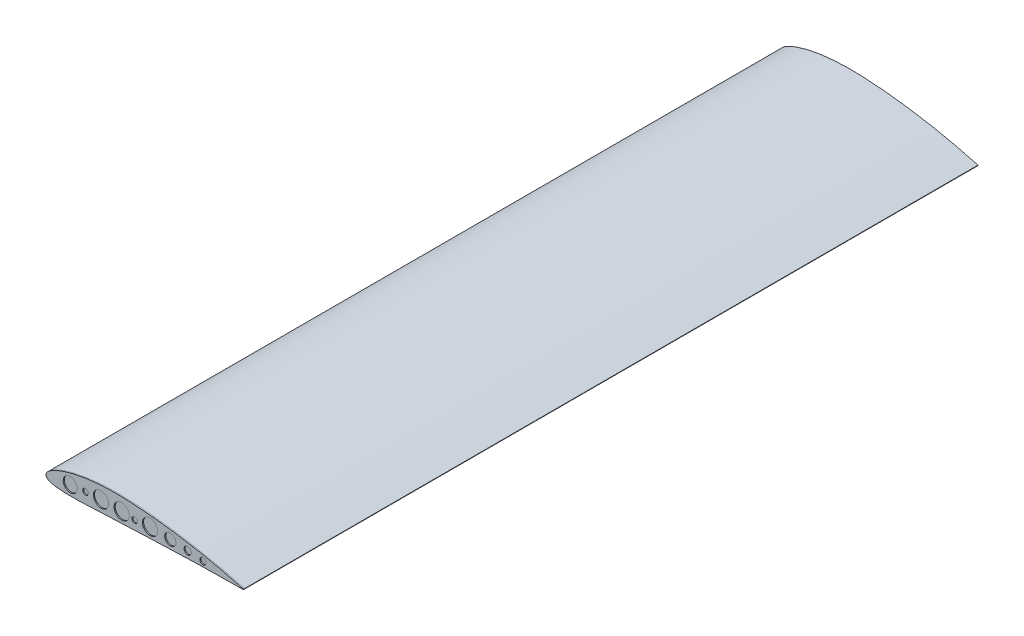
SolidWorks part; units mm, degrees
ref_plane "Спереди" through (0, 0, 0) normal (0, 0, 1) x (1, 0, 0)
ref_plane "Сверху" through (0, 0, 0) normal (0, 1, 0) x (1, 0, 0)
ref_plane "Справа" through (0, 0, 0) normal (1, 0, 0) x (0, 0, -1)
curve "Кривая1"
curve "Кривая2"
sketch "Эскиз1" plane through (0, 0, 0) normal (0, 0, 1) x (1, 0, 0)
  line L0 (350.0584, 0.4371) -> (349.9416, -0.4371)
  circle A0 centre (70, 10) radius 5
  circle A1 centre (157, 10) radius 5
  circle A2 centre (97.4967, 11.9444) radius 13.5
  circle A3 centre (134.0963, 11.9444) radius 13.5
  circle A4 centre (184.4175, 13.3257) radius 13.5
  circle A5 centre (42.9468, 7.3349) radius 12.5
  circle A6 centre (220.2781, 11.9444) radius 10
  circle A7 centre (251.1343, 10) radius 6.5
  circle A8 centre (278.0232, 7.3349) radius 5.5
  spline S0 degree 3 poles (-5446.8715, -2508.7969) (126.1492, 106.222) (-12.8915, 15.5996) (1.5868, -3.0408) (3.1128, -4.3174) (5.0932, -5.4477) (7.5057, -6.4459) (10.3511, -7.3163) (13.6202, -8.0629) (17.3047, -8.6899) (21.3937, -9.1993) (25.8754, -9.5951) (30.7367, -9.8833) (35.9641, -10.0678) (41.543, -10.1552) (47.4587, -10.1522) (53.6956, -10.0664) (60.2378, -9.9063) (67.069, -9.6797) (74.1728, -9.3973) (81.5318, -9.0687) (89.129, -8.7036) (96.9465, -8.3134) (104.9664, -7.9081) (113.1699, -7.4992) (121.5381, -7.0971) (130.0513, -6.7116) (138.7305, -6.3544) (147.5613, -6.023) (156.5187, -5.6608) (165.539, -5.2899) (174.5911, -4.913) (183.651, -4.5368) (192.6947, -4.1664) (201.6979, -3.8052) (210.6366, -3.4579) (219.4865, -3.1276) (228.2234, -2.8159) (236.8233, -2.526) (245.2625, -2.2578) (253.5175, -2.0131) (261.5654, -1.7909) (269.3836, -1.5915) (276.9501, -1.4144) (284.2431, -1.2577) (291.242, -1.1205) (297.9267, -1.0023) (304.2778, -0.8997) (310.2769, -0.8122) (315.9066, -0.7387) (321.1502, -0.6765) (325.9922, -0.6242) (330.4183, -0.5815) (334.4152, -0.5456) (337.971, -0.5171) (341.0748, -0.4941) (343.7174, -0.4754) (345.8906, -0.4615) (347.5879, -0.4511) (348.8039, -0.4436) (470.2745, 0.2435) (591.3157, 4.9751) (747.2137, -5974.9022) knots -0.181509 -0.181509 -0.181509 -0.181509 0.004621 0.009539 0.015079 0.02146 0.028815 0.037217 0.0467 0.057277 0.068945 0.081686 0.095481 0.110299 0.126106 0.142866 0.160538 0.179079 0.198444 0.218586 0.239458 0.261006 0.283182 0.305933 0.329205 0.352941 0.377085 0.40158 0.426714 0.452136 0.477716 0.503387 0.529081 0.554727 0.580259 0.605606 0.6307 0.655472 0.679854 0.703779 0.727181 0.749994 0.772155 0.793602 0.814272 0.834109 0.853054 0.871053 0.888055 0.904009 0.918869 0.932591 0.945134 0.956462 0.966538 0.975334 0.982823 0.988982 0.993791 0.997238 0.999309 2.025443 2.025443 2.025443 2.025443 only from (0, 0) to (349.9416, -0.4371) construction
  spline S1 degree 3 poles (2085.5087, 5741.6475) (435.8124, -34.4247) (394.0214, -11.7069) (348.9609, 0.741) (347.7876, 1.0648) (346.1489, 1.5135) (344.0486, 2.0844) (341.4919, 2.7716) (338.4852, 3.5709) (335.0354, 4.4738) (331.1514, 5.4747) (326.8426, 6.5647) (322.1195, 7.7348) (316.9943, 8.9771) (311.4795, 10.2804) (305.5895, 11.6361) (299.3393, 13.0339) (292.7446, 14.4627) (285.8231, 15.9138) (278.5923, 17.3751) (271.0714, 18.8365) (263.2804, 20.2892) (255.2397, 21.7208) (246.9711, 23.1239) (238.4966, 24.486) (229.8394, 25.8) (221.0228, 27.0546) (212.0713, 28.2428) (203.0092, 29.3543) (193.8618, 30.382) (184.6546, 31.3171) (175.4134, 32.1532) (166.1643, 32.8835) (156.9334, 33.5015) (147.7398, 34.0004) (138.5691, 34.3897) (129.4452, 34.5998) (120.4035, 34.6161) (111.5126, 34.4411) (102.8006, 34.0783) (94.2947, 33.5314) (86.0216, 32.8075) (78.0073, 31.9145) (70.2769, 30.8617) (62.8543, 29.6606) (55.7623, 28.3229) (49.0223, 26.8624) (42.6545, 25.2934) (36.677, 23.6312) (31.1071, 21.8907) (25.96, 20.0877) (21.2489, 18.2393) (16.9863, 16.3593) (13.1817, 14.4641) (9.8432, 12.5672) (6.9774, 10.6817) (4.5875, 8.8184) (2.6778, 6.9857) (1.2427, 5.1862) (0.3031, 3.4206) (-5.9667, -19.2767) (157.8244, -49.6104) (-5993.6515, 228.4557) knots -0.379848 -0.379848 -0.379848 -0.379848 0.000673 0.002688 0.00604 0.01072 0.016713 0.024005 0.032574 0.042394 0.053441 0.065681 0.079083 0.093606 0.109213 0.125858 0.143497 0.16208 0.181557 0.201873 0.222974 0.2448 0.267292 0.290389 0.314028 0.338143 0.362669 0.387537 0.412681 0.438032 0.463519 0.489073 0.514624 0.540102 0.565438 0.590624 0.615868 0.640767 0.665254 0.689266 0.712738 0.735606 0.757812 0.779295 0.8 0.819873 0.838862 0.85692 0.874001 0.890068 0.905081 0.91901 0.931831 0.943525 0.954082 0.963508 0.971818 0.979061 0.985315 0.990723 0.995508 1.175837 1.175837 1.175837 1.175837 only from (350.0584, 0.4371) to (0, 0) construction
  spline S2 degree 3 poles (0, 0) (0.1554, -0.5257) (0.4762, -1.611) (1.5868, -3.0408) (3.1128, -4.3174) (5.0932, -5.4477) (7.5057, -6.4459) (10.3511, -7.3163) (13.6202, -8.0629) (17.3047, -8.6899) (21.3937, -9.1993) (25.8754, -9.5951) (30.7367, -9.8833) (35.9641, -10.0678) (41.543, -10.1552) (47.4587, -10.1522) (53.6956, -10.0664) (60.2378, -9.9063) (67.069, -9.6797) (74.1728, -9.3973) (81.5318, -9.0687) (89.129, -8.7036) (96.9465, -8.3134) (104.9664, -7.9081) (113.1699, -7.4992) (121.5381, -7.0971) (130.0513, -6.7116) (138.7305, -6.3544) (147.5613, -6.023) (156.5187, -5.6608) (165.539, -5.2899) (174.5911, -4.913) (183.651, -4.5368) (192.6947, -4.1664) (201.6979, -3.8052) (210.6366, -3.4579) (219.4865, -3.1276) (228.2234, -2.8159) (236.8233, -2.526) (245.2625, -2.2578) (253.5175, -2.0131) (261.5654, -1.7909) (269.3836, -1.5915) (276.9501, -1.4144) (284.2431, -1.2577) (291.242, -1.1205) (297.9267, -1.0023) (304.2778, -0.8997) (310.2769, -0.8122) (315.9066, -0.7387) (321.1502, -0.6765) (325.9922, -0.6242) (330.4183, -0.5815) (334.4152, -0.5456) (337.971, -0.5171) (341.0748, -0.4941) (343.7174, -0.4754) (345.8906, -0.4615) (347.5879, -0.4511) (348.8039, -0.4436) (349.535, -0.4395) (349.8602, -0.4376) (349.9416, -0.4371) knots 0 0 0 0 0.004621 0.009539 0.015079 0.02146 0.028815 0.037217 0.0467 0.057277 0.068945 0.081686 0.095481 0.110299 0.126106 0.142866 0.160538 0.179079 0.198444 0.218586 0.239458 0.261006 0.283182 0.305933 0.329205 0.352941 0.377085 0.40158 0.426714 0.452136 0.477716 0.503387 0.529081 0.554727 0.580259 0.605606 0.6307 0.655472 0.679854 0.703779 0.727181 0.749994 0.772155 0.793602 0.814272 0.834109 0.853054 0.871053 0.888055 0.904009 0.918869 0.932591 0.945134 0.956462 0.966538 0.975334 0.982823 0.988982 0.993791 0.997238 0.999309 1 1 1 1
  spline S3 degree 3 poles (350.0584, 0.4371) (349.9799, 0.459) (349.6662, 0.5462) (348.9609, 0.741) (347.7876, 1.0648) (346.1489, 1.5135) (344.0486, 2.0844) (341.4919, 2.7716) (338.4852, 3.5709) (335.0354, 4.4738) (331.1514, 5.4747) (326.8426, 6.5647) (322.1195, 7.7348) (316.9943, 8.9771) (311.4795, 10.2804) (305.5895, 11.6361) (299.3393, 13.0339) (292.7446, 14.4627) (285.8231, 15.9138) (278.5923, 17.3751) (271.0714, 18.8365) (263.2804, 20.2892) (255.2397, 21.7208) (246.9711, 23.1239) (238.4966, 24.486) (229.8394, 25.8) (221.0228, 27.0546) (212.0713, 28.2428) (203.0092, 29.3543) (193.8618, 30.382) (184.6546, 31.3171) (175.4134, 32.1532) (166.1643, 32.8835) (156.9334, 33.5015) (147.7398, 34.0004) (138.5691, 34.3897) (129.4452, 34.5998) (120.4035, 34.6161) (111.5126, 34.4411) (102.8006, 34.0783) (94.2947, 33.5314) (86.0216, 32.8075) (78.0073, 31.9145) (70.2769, 30.8617) (62.8543, 29.6606) (55.7623, 28.3229) (49.0223, 26.8624) (42.6545, 25.2934) (36.677, 23.6312) (31.1071, 21.8907) (25.96, 20.0877) (21.2489, 18.2393) (16.9863, 16.3593) (13.1817, 14.4641) (9.8432, 12.5672) (6.9774, 10.6817) (4.5875, 8.8184) (2.6778, 6.9857) (1.2427, 5.1862) (0.3031, 3.4206) (-0.1802, 1.6712) (-0.0588, 0.5452) (0, 0) knots 0 0 0 0 0.000673 0.002688 0.00604 0.01072 0.016713 0.024005 0.032574 0.042394 0.053441 0.065681 0.079083 0.093606 0.109213 0.125858 0.143497 0.16208 0.181557 0.201873 0.222974 0.2448 0.267292 0.290389 0.314028 0.338143 0.362669 0.387537 0.412681 0.438032 0.463519 0.489073 0.514624 0.540102 0.565438 0.590624 0.615868 0.640767 0.665254 0.689266 0.712738 0.735606 0.757812 0.779295 0.8 0.819873 0.838862 0.85692 0.874001 0.890068 0.905081 0.91901 0.931831 0.943525 0.954082 0.963508 0.971818 0.979061 0.985315 0.990723 0.995508 1 1 1 1
  dimension "D1" = 10
  dimension "D2" = 10
  dimension "D7" = 25
  dimension "D8" = 27
  dimension "D9" = 27
  dimension "D10" = 27
  dimension "D11" = 20
  dimension "D12" = 13
  dimension "D13" = 11
  dimension "D3" = 10
  dimension "D4" = 70
  dimension "D5" = 157
  dimension "D6" = 10
  dimension "D14" = 7.3349
  dimension "D15" = 11.9444
  dimension "D16" = 27.0532
  dimension "D17" = 27.4967
  dimension "D18" = 36.5995
  dimension "D19" = 11.9444
  dimension "D20" = 27.4175
  dimension "D21" = 3.3257
  dimension "D22" = 35.8606
  dimension "D23" = 30.8562
  dimension "D24" = 10
  dimension "D25" = 2.6651
  dimension "D26" = 26.8889
  dimension "D27" = 1.9444
ref_plane "Плоскость8" through (0, 0, 162.5) normal (0, 0, 1) x (1, 0, 0)
ref_plane "Плоскость9" through (0, 0, 325) normal (0, 0, 1) x (1, 0, 0)
ref_plane "Плоскость10" through (0, 0, 487.5) normal (0, 0, 1) x (1, 0, 0)
ref_plane "Плоскость11" through (0, 0, 650) normal (0, 0, 1) x (1, 0, 0)
ref_plane "Плоскость12" through (0, 0, 812.5) normal (0, 0, 1) x (1, 0, 0)
ref_plane "Плоскость13" through (0, 0, 975) normal (0, 0, 1) x (1, 0, 0)
ref_plane "Плоскость14" through (0, 0, 1137.5) normal (0, 0, 1) x (1, 0, 0)
sketch "Эскиз4" plane through (0, 0, 162.5) normal (0, 0, 1) x (1, 0, 0)
  line L0 (350.0584, 0.4371) -> (349.9416, -0.4371)
  circle A0 centre (70, 10) radius 5
  circle A1 centre (157, 10) radius 5
  circle A2 centre (97.4967, 11.9444) radius 13.5
  circle A3 centre (134.0963, 11.9444) radius 13.5
  circle A4 centre (184.4175, 13.3257) radius 13.5
  circle A5 centre (42.9468, 7.3349) radius 12.5
  circle A6 centre (220.2781, 11.9444) radius 10
  circle A7 centre (251.1343, 10) radius 6.5
  circle A8 centre (278.0232, 7.3349) radius 5.5
  spline S2 degree 3 poles (0, 0) (0.1554, -0.5257) (0.4762, -1.611) (1.5868, -3.0408) (3.1128, -4.3174) (5.0932, -5.4477) (7.5057, -6.4459) (10.3511, -7.3163) (13.6202, -8.0629) (17.3047, -8.6899) (21.3937, -9.1993) (25.8754, -9.5951) (30.7367, -9.8833) (35.9641, -10.0678) (41.543, -10.1552) (47.4587, -10.1522) (53.6956, -10.0664) (60.2378, -9.9063) (67.069, -9.6797) (74.1728, -9.3973) (81.5318, -9.0687) (89.129, -8.7036) (96.9465, -8.3134) (104.9664, -7.9081) (113.1699, -7.4992) (121.5381, -7.0971) (130.0513, -6.7116) (138.7305, -6.3544) (147.5613, -6.023) (156.5187, -5.6608) (165.539, -5.2899) (174.5911, -4.913) (183.651, -4.5368) (192.6947, -4.1664) (201.6979, -3.8052) (210.6366, -3.4579) (219.4865, -3.1276) (228.2234, -2.8159) (236.8233, -2.526) (245.2625, -2.2578) (253.5175, -2.0131) (261.5654, -1.7909) (269.3836, -1.5915) (276.9501, -1.4144) (284.2431, -1.2577) (291.242, -1.1205) (297.9267, -1.0023) (304.2778, -0.8997) (310.2769, -0.8122) (315.9066, -0.7387) (321.1502, -0.6765) (325.9922, -0.6242) (330.4183, -0.5815) (334.4152, -0.5456) (337.971, -0.5171) (341.0748, -0.4941) (343.7174, -0.4754) (345.8906, -0.4615) (347.5879, -0.4511) (348.8039, -0.4436) (349.535, -0.4395) (349.8602, -0.4376) (349.9416, -0.4371) knots 0 0 0 0 0.004621 0.009539 0.015079 0.02146 0.028815 0.037217 0.0467 0.057277 0.068945 0.081686 0.095481 0.110299 0.126106 0.142866 0.160538 0.179079 0.198444 0.218586 0.239458 0.261006 0.283182 0.305933 0.329205 0.352941 0.377085 0.40158 0.426714 0.452136 0.477716 0.503387 0.529081 0.554727 0.580259 0.605606 0.6307 0.655472 0.679854 0.703779 0.727181 0.749994 0.772155 0.793602 0.814272 0.834109 0.853054 0.871053 0.888055 0.904009 0.918869 0.932591 0.945134 0.956462 0.966538 0.975334 0.982823 0.988982 0.993791 0.997238 0.999309 1 1 1 1
  spline S3 degree 3 poles (350.0584, 0.4372) (349.9799, 0.459) (349.6662, 0.5462) (348.9609, 0.741) (347.7876, 1.0648) (346.1489, 1.5135) (344.0486, 2.0844) (341.4919, 2.7716) (338.4852, 3.5709) (335.0354, 4.4738) (331.1514, 5.4747) (326.8426, 6.5647) (322.1195, 7.7348) (316.9943, 8.9771) (311.4795, 10.2804) (305.5895, 11.6361) (299.3393, 13.0339) (292.7446, 14.4627) (285.8231, 15.9138) (278.5923, 17.3751) (271.0714, 18.8365) (263.2804, 20.2892) (255.2397, 21.7208) (246.9711, 23.1239) (238.4966, 24.486) (229.8394, 25.8) (221.0228, 27.0546) (212.0713, 28.2428) (203.0092, 29.3543) (193.8618, 30.382) (184.6546, 31.3171) (175.4134, 32.1532) (166.1643, 32.8835) (156.9334, 33.5015) (147.7398, 34.0004) (138.5691, 34.3897) (129.4452, 34.5998) (120.4035, 34.6161) (111.5126, 34.4411) (102.8006, 34.0783) (94.2947, 33.5314) (86.0216, 32.8075) (78.0073, 31.9145) (70.2769, 30.8617) (62.8543, 29.6606) (55.7623, 28.3229) (49.0223, 26.8624) (42.6545, 25.2934) (36.677, 23.6312) (31.1071, 21.8907) (25.96, 20.0877) (21.2489, 18.2393) (16.9863, 16.3593) (13.1817, 14.4641) (9.8432, 12.5672) (6.9774, 10.6817) (4.5875, 8.8184) (2.6778, 6.9857) (1.2427, 5.1862) (0.3031, 3.4206) (-0.1802, 1.6712) (-0.0588, 0.5452) (0, 0) knots 0 0 0 0 0.000673 0.002688 0.00604 0.01072 0.016713 0.024005 0.032574 0.042394 0.053441 0.065681 0.079083 0.093606 0.109213 0.125858 0.143497 0.16208 0.181557 0.201873 0.222974 0.2448 0.267292 0.290389 0.314028 0.338143 0.362669 0.387537 0.412681 0.438032 0.463519 0.489073 0.514624 0.540102 0.565438 0.590624 0.615868 0.640767 0.665254 0.689266 0.712738 0.735606 0.757812 0.779295 0.8 0.819873 0.838862 0.85692 0.874001 0.890068 0.905081 0.91901 0.931831 0.943525 0.954082 0.963508 0.971818 0.979061 0.985315 0.990723 0.995508 1 1 1 1
  dimension "D1" = 10
  dimension "D2" = 10
  dimension "D7" = 25
  dimension "D8" = 27
  dimension "D9" = 27
  dimension "D10" = 27
  dimension "D11" = 20
  dimension "D12" = 13
  dimension "D13" = 11
  dimension "D3" = 10
  dimension "D4" = 70
  dimension "D5" = 157
  dimension "D6" = 10
  dimension "D14" = 7.3349
  dimension "D15" = 11.9444
  dimension "D16" = 27.0532
  dimension "D17" = 27.4967
  dimension "D18" = 36.5995
  dimension "D19" = 11.9444
  dimension "D20" = 27.4175
  dimension "D21" = 3.3257
  dimension "D22" = 35.8606
  dimension "D23" = 30.8562
  dimension "D24" = 10
  dimension "D25" = 2.6651
  dimension "D26" = 26.8889
  dimension "D27" = 1.9444
  dimension "D28" = 0.8743
  dimension "D29" = 349.9416
  dimension "D30" = 350.0584
  dimension "D32" = 0.4371
sketch "Эскиз5" plane through (0, 0, 325) normal (0, 0, 1) x (1, 0, 0)
  line L0 (350.0585, 0.4371) -> (349.9416, -0.4372)
  circle A0 centre (70, 10) radius 5
  circle A1 centre (157, 10) radius 5
  circle A2 centre (97.4967, 11.9444) radius 13.5
  circle A3 centre (134.0963, 11.9444) radius 13.5
  circle A4 centre (184.4175, 13.3257) radius 13.5
  circle A5 centre (42.9468, 7.3349) radius 12.5
  circle A6 centre (220.2781, 11.9444) radius 10
  circle A7 centre (251.1343, 10) radius 6.5
  circle A8 centre (278.0232, 7.3349) radius 5.5
  spline S2 degree 3 poles (0, 0) (0.1554, -0.5257) (0.4762, -1.611) (1.5868, -3.0408) (3.1128, -4.3174) (5.0932, -5.4477) (7.5057, -6.4459) (10.3511, -7.3163) (13.6202, -8.0629) (17.3047, -8.6899) (21.3937, -9.1993) (25.8754, -9.5951) (30.7367, -9.8833) (35.9641, -10.0678) (41.543, -10.1552) (47.4587, -10.1522) (53.6956, -10.0664) (60.2378, -9.9063) (67.069, -9.6797) (74.1728, -9.3973) (81.5318, -9.0687) (89.129, -8.7036) (96.9465, -8.3134) (104.9664, -7.9081) (113.1699, -7.4992) (121.5381, -7.0971) (130.0513, -6.7116) (138.7305, -6.3544) (147.5613, -6.023) (156.5187, -5.6608) (165.539, -5.2899) (174.5911, -4.913) (183.651, -4.5368) (192.6947, -4.1664) (201.6979, -3.8052) (210.6366, -3.4579) (219.4865, -3.1276) (228.2234, -2.8159) (236.8233, -2.526) (245.2625, -2.2578) (253.5175, -2.0131) (261.5654, -1.7909) (269.3836, -1.5915) (276.9501, -1.4144) (284.2431, -1.2577) (291.242, -1.1205) (297.9267, -1.0023) (304.2778, -0.8997) (310.2769, -0.8122) (315.9066, -0.7387) (321.1502, -0.6765) (325.9922, -0.6242) (330.4183, -0.5815) (334.4152, -0.5456) (337.971, -0.5171) (341.0748, -0.4941) (343.7174, -0.4754) (345.8906, -0.4615) (347.5879, -0.4511) (348.8039, -0.4436) (349.535, -0.4395) (349.8602, -0.4376) (349.9416, -0.4372) knots 0 0 0 0 0.004621 0.009539 0.015079 0.02146 0.028815 0.037217 0.0467 0.057277 0.068945 0.081686 0.095481 0.110299 0.126106 0.142866 0.160538 0.179079 0.198444 0.218586 0.239458 0.261006 0.283182 0.305933 0.329205 0.352941 0.377085 0.40158 0.426714 0.452136 0.477716 0.503387 0.529081 0.554727 0.580259 0.605606 0.6307 0.655472 0.679854 0.703779 0.727181 0.749994 0.772155 0.793602 0.814272 0.834109 0.853054 0.871053 0.888055 0.904009 0.918869 0.932591 0.945134 0.956462 0.966538 0.975334 0.982823 0.988982 0.993791 0.997238 0.999309 1 1 1 1
  spline S3 degree 3 poles (350.0585, 0.4371) (349.9799, 0.459) (349.6662, 0.5462) (348.9609, 0.741) (347.7876, 1.0648) (346.1489, 1.5135) (344.0486, 2.0844) (341.4919, 2.7716) (338.4852, 3.5709) (335.0354, 4.4738) (331.1514, 5.4747) (326.8426, 6.5647) (322.1195, 7.7348) (316.9943, 8.9771) (311.4795, 10.2804) (305.5895, 11.6361) (299.3393, 13.0339) (292.7446, 14.4627) (285.8231, 15.9138) (278.5923, 17.3751) (271.0714, 18.8365) (263.2804, 20.2892) (255.2397, 21.7208) (246.9711, 23.1239) (238.4966, 24.486) (229.8394, 25.8) (221.0228, 27.0546) (212.0713, 28.2428) (203.0092, 29.3543) (193.8618, 30.382) (184.6546, 31.3171) (175.4134, 32.1532) (166.1643, 32.8835) (156.9334, 33.5015) (147.7398, 34.0004) (138.5691, 34.3897) (129.4452, 34.5998) (120.4035, 34.6161) (111.5126, 34.4411) (102.8006, 34.0783) (94.2947, 33.5314) (86.0216, 32.8075) (78.0073, 31.9145) (70.2769, 30.8617) (62.8543, 29.6606) (55.7623, 28.3229) (49.0223, 26.8624) (42.6545, 25.2934) (36.677, 23.6312) (31.1071, 21.8907) (25.96, 20.0877) (21.2489, 18.2393) (16.9863, 16.3593) (13.1817, 14.4641) (9.8432, 12.5672) (6.9774, 10.6817) (4.5875, 8.8184) (2.6778, 6.9857) (1.2427, 5.1862) (0.3031, 3.4206) (-0.1802, 1.6712) (-0.0588, 0.5452) (0, 0) knots 0 0 0 0 0.000673 0.002688 0.00604 0.01072 0.016713 0.024005 0.032574 0.042394 0.053441 0.065681 0.079083 0.093606 0.109213 0.125858 0.143497 0.16208 0.181557 0.201873 0.222974 0.2448 0.267292 0.290389 0.314028 0.338143 0.362669 0.387537 0.412681 0.438032 0.463519 0.489073 0.514624 0.540102 0.565438 0.590624 0.615868 0.640767 0.665254 0.689266 0.712738 0.735606 0.757812 0.779295 0.8 0.819873 0.838862 0.85692 0.874001 0.890068 0.905081 0.91901 0.931831 0.943525 0.954082 0.963508 0.971818 0.979061 0.985315 0.990723 0.995508 1 1 1 1
  dimension "D1" = 10
  dimension "D2" = 10
  dimension "D7" = 25
  dimension "D8" = 27
  dimension "D9" = 27
  dimension "D10" = 27
  dimension "D11" = 20
  dimension "D12" = 13
  dimension "D13" = 11
  dimension "D3" = 10
  dimension "D4" = 70
  dimension "D5" = 157
  dimension "D6" = 10
  dimension "D14" = 7.3349
  dimension "D15" = 11.9444
  dimension "D16" = 27.0532
  dimension "D17" = 27.4967
  dimension "D18" = 36.5995
  dimension "D19" = 11.9444
  dimension "D20" = 27.4175
  dimension "D21" = 3.3257
  dimension "D22" = 35.8606
  dimension "D23" = 30.8562
  dimension "D24" = 10
  dimension "D25" = 2.6651
  dimension "D26" = 26.8889
  dimension "D27" = 1.9444
  dimension "D28" = 349.9416
  dimension "D29" = 350.0584
  dimension "D30" = 0.4371
  dimension "D31" = 0.8821
sketch "Эскиз6" plane through (0, 0, 487.5) normal (0, 0, 1) x (1, 0, 0)
  line L0 (350.0584, 0.4371) -> (349.9416, -0.4372)
  circle A0 centre (70, 10) radius 5
  circle A1 centre (157, 10) radius 5
  circle A2 centre (97.4967, 11.9444) radius 13.5
  circle A3 centre (134.0963, 11.9444) radius 13.5
  circle A4 centre (184.4175, 13.3257) radius 13.5
  circle A5 centre (42.9468, 7.3349) radius 12.5
  circle A6 centre (220.2781, 11.9444) radius 10
  circle A7 centre (251.1343, 10) radius 6.5
  circle A8 centre (278.0232, 7.3349) radius 5.5
  spline S2 degree 3 poles (0, 0) (0.1554, -0.5257) (0.4762, -1.611) (1.5868, -3.0408) (3.1128, -4.3174) (5.0932, -5.4477) (7.5057, -6.4459) (10.3511, -7.3163) (13.6202, -8.0629) (17.3047, -8.6899) (21.3937, -9.1993) (25.8754, -9.5951) (30.7367, -9.8833) (35.9641, -10.0678) (41.543, -10.1552) (47.4587, -10.1522) (53.6956, -10.0664) (60.2378, -9.9063) (67.069, -9.6797) (74.1728, -9.3973) (81.5318, -9.0687) (89.129, -8.7036) (96.9465, -8.3134) (104.9664, -7.9081) (113.1699, -7.4992) (121.5381, -7.0971) (130.0513, -6.7116) (138.7305, -6.3544) (147.5613, -6.023) (156.5187, -5.6608) (165.539, -5.2899) (174.5911, -4.913) (183.651, -4.5368) (192.6947, -4.1664) (201.6979, -3.8052) (210.6366, -3.4579) (219.4865, -3.1276) (228.2234, -2.8159) (236.8233, -2.526) (245.2625, -2.2578) (253.5175, -2.0131) (261.5654, -1.7909) (269.3836, -1.5915) (276.9501, -1.4144) (284.2431, -1.2577) (291.242, -1.1205) (297.9267, -1.0023) (304.2778, -0.8997) (310.2769, -0.8122) (315.9066, -0.7387) (321.1502, -0.6765) (325.9922, -0.6242) (330.4183, -0.5815) (334.4152, -0.5456) (337.971, -0.5171) (341.0748, -0.4941) (343.7174, -0.4754) (345.8906, -0.4615) (347.5879, -0.4511) (348.8039, -0.4436) (349.535, -0.4395) (349.8602, -0.4376) (349.9416, -0.4372) knots 0 0 0 0 0.004621 0.009539 0.015079 0.02146 0.028815 0.037217 0.0467 0.057277 0.068945 0.081686 0.095481 0.110299 0.126106 0.142866 0.160538 0.179079 0.198444 0.218586 0.239458 0.261006 0.283182 0.305933 0.329205 0.352941 0.377085 0.40158 0.426714 0.452136 0.477716 0.503387 0.529081 0.554727 0.580259 0.605606 0.6307 0.655472 0.679854 0.703779 0.727181 0.749994 0.772155 0.793602 0.814272 0.834109 0.853054 0.871053 0.888055 0.904009 0.918869 0.932591 0.945134 0.956462 0.966538 0.975334 0.982823 0.988982 0.993791 0.997238 0.999309 1 1 1 1
  spline S3 degree 3 poles (350.0584, 0.4371) (349.9799, 0.459) (349.6662, 0.5462) (348.9609, 0.741) (347.7876, 1.0648) (346.1489, 1.5135) (344.0486, 2.0844) (341.4919, 2.7716) (338.4852, 3.5709) (335.0354, 4.4738) (331.1514, 5.4747) (326.8426, 6.5647) (322.1195, 7.7348) (316.9943, 8.9771) (311.4795, 10.2804) (305.5895, 11.6361) (299.3393, 13.0339) (292.7446, 14.4627) (285.8231, 15.9138) (278.5923, 17.3751) (271.0714, 18.8365) (263.2804, 20.2892) (255.2397, 21.7208) (246.9711, 23.1239) (238.4966, 24.486) (229.8394, 25.8) (221.0228, 27.0546) (212.0713, 28.2428) (203.0092, 29.3543) (193.8618, 30.382) (184.6546, 31.3171) (175.4134, 32.1532) (166.1643, 32.8835) (156.9334, 33.5015) (147.7398, 34.0004) (138.5691, 34.3897) (129.4452, 34.5998) (120.4035, 34.6161) (111.5126, 34.4411) (102.8006, 34.0783) (94.2947, 33.5314) (86.0216, 32.8075) (78.0073, 31.9145) (70.2769, 30.8617) (62.8543, 29.6606) (55.7623, 28.3229) (49.0223, 26.8624) (42.6545, 25.2934) (36.677, 23.6312) (31.1071, 21.8907) (25.96, 20.0877) (21.2489, 18.2393) (16.9863, 16.3593) (13.1817, 14.4641) (9.8432, 12.5672) (6.9774, 10.6817) (4.5875, 8.8184) (2.6778, 6.9857) (1.2427, 5.1862) (0.3031, 3.4206) (-0.1802, 1.6712) (-0.0588, 0.5452) (0, 0) knots 0 0 0 0 0.000673 0.002688 0.00604 0.01072 0.016713 0.024005 0.032574 0.042394 0.053441 0.065681 0.079083 0.093606 0.109213 0.125858 0.143497 0.16208 0.181557 0.201873 0.222974 0.2448 0.267292 0.290389 0.314028 0.338143 0.362669 0.387537 0.412681 0.438032 0.463519 0.489073 0.514624 0.540102 0.565438 0.590624 0.615868 0.640767 0.665254 0.689266 0.712738 0.735606 0.757812 0.779295 0.8 0.819873 0.838862 0.85692 0.874001 0.890068 0.905081 0.91901 0.931831 0.943525 0.954082 0.963508 0.971818 0.979061 0.985315 0.990723 0.995508 1 1 1 1
  dimension "D1" = 10
  dimension "D2" = 10
  dimension "D7" = 25
  dimension "D8" = 27
  dimension "D9" = 27
  dimension "D10" = 27
  dimension "D11" = 20
  dimension "D12" = 13
  dimension "D13" = 11
  dimension "D3" = 10
  dimension "D4" = 70
  dimension "D5" = 157
  dimension "D6" = 10
  dimension "D14" = 7.3349
  dimension "D15" = 11.9444
  dimension "D16" = 27.0532
  dimension "D17" = 27.4967
  dimension "D18" = 36.5995
  dimension "D19" = 11.9444
  dimension "D20" = 27.4175
  dimension "D21" = 3.3257
  dimension "D22" = 35.8606
  dimension "D23" = 30.8562
  dimension "D24" = 10
  dimension "D25" = 2.6651
  dimension "D26" = 26.8889
  dimension "D27" = 1.9444
  dimension "D28" = 0.8821
  dimension "D29" = 349.9416
  dimension "D30" = 350.0587
  dimension "D31" = 0.4371
sketch "Эскиз7" plane through (0, 0, 650) normal (0, 0, 1) x (1, 0, 0)
  line L0 (350.0584, 0.4371) -> (349.9416, -0.4372)
  circle A0 centre (70, 10) radius 5
  circle A1 centre (157, 10) radius 5
  circle A2 centre (97.4967, 11.9444) radius 13.5
  circle A3 centre (134.0963, 11.9444) radius 13.5
  circle A4 centre (184.4175, 13.3257) radius 13.5
  circle A5 centre (42.9468, 7.3349) radius 12.5
  circle A6 centre (220.2781, 11.9444) radius 10
  circle A7 centre (251.1343, 10) radius 6.5
  circle A8 centre (278.0232, 7.3349) radius 5.5
  spline S2 degree 3 poles (0, 0) (0.1554, -0.5257) (0.4762, -1.611) (1.5868, -3.0408) (3.1128, -4.3174) (5.0932, -5.4477) (7.5057, -6.4459) (10.3511, -7.3163) (13.6202, -8.0629) (17.3047, -8.6899) (21.3937, -9.1993) (25.8754, -9.5951) (30.7367, -9.8833) (35.9641, -10.0678) (41.543, -10.1552) (47.4587, -10.1522) (53.6956, -10.0664) (60.2378, -9.9063) (67.069, -9.6797) (74.1728, -9.3973) (81.5318, -9.0687) (89.129, -8.7036) (96.9465, -8.3134) (104.9664, -7.9081) (113.1699, -7.4992) (121.5381, -7.0971) (130.0513, -6.7116) (138.7305, -6.3544) (147.5613, -6.023) (156.5187, -5.6608) (165.539, -5.2899) (174.5911, -4.913) (183.651, -4.5368) (192.6947, -4.1664) (201.6979, -3.8052) (210.6366, -3.4579) (219.4865, -3.1276) (228.2234, -2.8159) (236.8233, -2.526) (245.2625, -2.2578) (253.5175, -2.0131) (261.5654, -1.7909) (269.3836, -1.5915) (276.9501, -1.4144) (284.2431, -1.2577) (291.242, -1.1205) (297.9267, -1.0023) (304.2778, -0.8997) (310.2769, -0.8122) (315.9066, -0.7387) (321.1502, -0.6765) (325.9922, -0.6242) (330.4183, -0.5815) (334.4152, -0.5456) (337.971, -0.5171) (341.0748, -0.4941) (343.7174, -0.4754) (345.8906, -0.4615) (347.5879, -0.4511) (348.8039, -0.4436) (349.535, -0.4395) (349.8602, -0.4376) (349.9416, -0.4372) knots 0 0 0 0 0.004621 0.009539 0.015079 0.02146 0.028815 0.037217 0.0467 0.057277 0.068945 0.081686 0.095481 0.110299 0.126106 0.142866 0.160538 0.179079 0.198444 0.218586 0.239458 0.261006 0.283182 0.305933 0.329205 0.352941 0.377085 0.40158 0.426714 0.452136 0.477716 0.503387 0.529081 0.554727 0.580259 0.605606 0.6307 0.655472 0.679854 0.703779 0.727181 0.749994 0.772155 0.793602 0.814272 0.834109 0.853054 0.871053 0.888055 0.904009 0.918869 0.932591 0.945134 0.956462 0.966538 0.975334 0.982823 0.988982 0.993791 0.997238 0.999309 1 1 1 1
  spline S3 degree 3 poles (350.0584, 0.4371) (349.9799, 0.459) (349.6662, 0.5462) (348.9609, 0.741) (347.7876, 1.0648) (346.1489, 1.5135) (344.0486, 2.0844) (341.4919, 2.7716) (338.4852, 3.5709) (335.0354, 4.4738) (331.1514, 5.4747) (326.8426, 6.5647) (322.1195, 7.7348) (316.9943, 8.9771) (311.4795, 10.2804) (305.5895, 11.6361) (299.3393, 13.0339) (292.7446, 14.4627) (285.8231, 15.9138) (278.5923, 17.3751) (271.0714, 18.8365) (263.2804, 20.2892) (255.2397, 21.7208) (246.9711, 23.1239) (238.4966, 24.486) (229.8394, 25.8) (221.0228, 27.0546) (212.0713, 28.2428) (203.0092, 29.3543) (193.8618, 30.382) (184.6546, 31.3171) (175.4134, 32.1532) (166.1643, 32.8835) (156.9334, 33.5015) (147.7398, 34.0004) (138.5691, 34.3897) (129.4452, 34.5998) (120.4035, 34.6161) (111.5126, 34.4411) (102.8006, 34.0783) (94.2947, 33.5314) (86.0216, 32.8075) (78.0073, 31.9145) (70.2769, 30.8617) (62.8543, 29.6606) (55.7623, 28.3229) (49.0223, 26.8624) (42.6545, 25.2934) (36.677, 23.6312) (31.1071, 21.8907) (25.96, 20.0877) (21.2489, 18.2393) (16.9863, 16.3593) (13.1817, 14.4641) (9.8432, 12.5672) (6.9774, 10.6817) (4.5875, 8.8184) (2.6778, 6.9857) (1.2427, 5.1862) (0.3031, 3.4206) (-0.1802, 1.6712) (-0.0588, 0.5452) (0, 0) knots 0 0 0 0 0.000673 0.002688 0.00604 0.01072 0.016713 0.024005 0.032574 0.042394 0.053441 0.065681 0.079083 0.093606 0.109213 0.125858 0.143497 0.16208 0.181557 0.201873 0.222974 0.2448 0.267292 0.290389 0.314028 0.338143 0.362669 0.387537 0.412681 0.438032 0.463519 0.489073 0.514624 0.540102 0.565438 0.590624 0.615868 0.640767 0.665254 0.689266 0.712738 0.735606 0.757812 0.779295 0.8 0.819873 0.838862 0.85692 0.874001 0.890068 0.905081 0.91901 0.931831 0.943525 0.954082 0.963508 0.971818 0.979061 0.985315 0.990723 0.995508 1 1 1 1
  dimension "D1" = 10
  dimension "D2" = 10
  dimension "D7" = 25
  dimension "D8" = 27
  dimension "D9" = 27
  dimension "D10" = 27
  dimension "D11" = 20
  dimension "D12" = 13
  dimension "D13" = 11
  dimension "D3" = 10
  dimension "D4" = 70
  dimension "D5" = 157
  dimension "D6" = 10
  dimension "D14" = 7.3349
  dimension "D15" = 11.9444
  dimension "D16" = 27.0532
  dimension "D17" = 27.4967
  dimension "D18" = 36.5995
  dimension "D19" = 11.9444
  dimension "D20" = 27.4175
  dimension "D21" = 3.3257
  dimension "D22" = 35.8606
  dimension "D23" = 30.8562
  dimension "D24" = 10
  dimension "D25" = 2.6651
  dimension "D26" = 26.8889
  dimension "D27" = 1.9444
  dimension "D28" = 0.8821
  dimension "D29" = 349.9416
  dimension "D30" = 350.0584
  dimension "D31" = 0.4371
sketch "Эскиз8" plane through (0, 0, 812.5) normal (0, 0, 1) x (1, 0, 0)
  line L0 (350.0584, 0.4371) -> (349.9416, -0.4372)
  circle A0 centre (70, 10) radius 5
  circle A1 centre (157, 10) radius 5
  circle A2 centre (97.4967, 11.9444) radius 13.5
  circle A3 centre (134.0963, 11.9444) radius 13.5
  circle A4 centre (184.4175, 13.3257) radius 13.5
  circle A5 centre (42.9468, 7.3349) radius 12.5
  circle A6 centre (220.2781, 11.9444) radius 10
  circle A7 centre (251.1343, 10) radius 6.5
  circle A8 centre (278.0232, 7.3349) radius 5.5
  spline S2 degree 3 poles (0, 0) (0.1554, -0.5257) (0.4762, -1.611) (1.5868, -3.0408) (3.1128, -4.3174) (5.0932, -5.4477) (7.5057, -6.4459) (10.3511, -7.3163) (13.6202, -8.0629) (17.3047, -8.6899) (21.3937, -9.1993) (25.8754, -9.5951) (30.7367, -9.8833) (35.9641, -10.0678) (41.543, -10.1552) (47.4587, -10.1522) (53.6956, -10.0664) (60.2378, -9.9063) (67.069, -9.6797) (74.1728, -9.3973) (81.5318, -9.0687) (89.129, -8.7036) (96.9465, -8.3134) (104.9664, -7.9081) (113.1699, -7.4992) (121.5381, -7.0971) (130.0513, -6.7116) (138.7305, -6.3544) (147.5613, -6.023) (156.5187, -5.6608) (165.539, -5.2899) (174.5911, -4.913) (183.651, -4.5368) (192.6947, -4.1664) (201.6979, -3.8052) (210.6366, -3.4579) (219.4865, -3.1276) (228.2234, -2.8159) (236.8233, -2.526) (245.2625, -2.2578) (253.5175, -2.0131) (261.5654, -1.7909) (269.3836, -1.5915) (276.9501, -1.4144) (284.2431, -1.2577) (291.242, -1.1205) (297.9267, -1.0023) (304.2778, -0.8997) (310.2769, -0.8122) (315.9066, -0.7387) (321.1502, -0.6765) (325.9922, -0.6242) (330.4183, -0.5815) (334.4152, -0.5456) (337.971, -0.5171) (341.0748, -0.4941) (343.7174, -0.4754) (345.8906, -0.4615) (347.5879, -0.4511) (348.8039, -0.4436) (349.535, -0.4395) (349.8602, -0.4376) (349.9416, -0.4372) knots 0 0 0 0 0.004621 0.009539 0.015079 0.02146 0.028815 0.037217 0.0467 0.057277 0.068945 0.081686 0.095481 0.110299 0.126106 0.142866 0.160538 0.179079 0.198444 0.218586 0.239458 0.261006 0.283182 0.305933 0.329205 0.352941 0.377085 0.40158 0.426714 0.452136 0.477716 0.503387 0.529081 0.554727 0.580259 0.605606 0.6307 0.655472 0.679854 0.703779 0.727181 0.749994 0.772155 0.793602 0.814272 0.834109 0.853054 0.871053 0.888055 0.904009 0.918869 0.932591 0.945134 0.956462 0.966538 0.975334 0.982823 0.988982 0.993791 0.997238 0.999309 1 1 1 1
  spline S3 degree 3 poles (350.0584, 0.4371) (349.9799, 0.459) (349.6662, 0.5462) (348.9609, 0.741) (347.7876, 1.0648) (346.1489, 1.5135) (344.0486, 2.0844) (341.4919, 2.7716) (338.4852, 3.5709) (335.0354, 4.4738) (331.1514, 5.4747) (326.8426, 6.5647) (322.1195, 7.7348) (316.9943, 8.9771) (311.4795, 10.2804) (305.5895, 11.6361) (299.3393, 13.0339) (292.7446, 14.4627) (285.8231, 15.9138) (278.5923, 17.3751) (271.0714, 18.8365) (263.2804, 20.2892) (255.2397, 21.7208) (246.9711, 23.1239) (238.4966, 24.486) (229.8394, 25.8) (221.0228, 27.0546) (212.0713, 28.2428) (203.0092, 29.3543) (193.8618, 30.382) (184.6546, 31.3171) (175.4134, 32.1532) (166.1643, 32.8835) (156.9334, 33.5015) (147.7398, 34.0004) (138.5691, 34.3897) (129.4452, 34.5998) (120.4035, 34.6161) (111.5126, 34.4411) (102.8006, 34.0783) (94.2947, 33.5314) (86.0216, 32.8075) (78.0073, 31.9145) (70.2769, 30.8617) (62.8543, 29.6606) (55.7623, 28.3229) (49.0223, 26.8624) (42.6545, 25.2934) (36.677, 23.6312) (31.1071, 21.8907) (25.96, 20.0877) (21.2489, 18.2393) (16.9863, 16.3593) (13.1817, 14.4641) (9.8432, 12.5672) (6.9774, 10.6817) (4.5875, 8.8184) (2.6778, 6.9857) (1.2427, 5.1862) (0.3031, 3.4206) (-0.1802, 1.6712) (-0.0588, 0.5452) (0, 0) knots 0 0 0 0 0.000673 0.002688 0.00604 0.01072 0.016713 0.024005 0.032574 0.042394 0.053441 0.065681 0.079083 0.093606 0.109213 0.125858 0.143497 0.16208 0.181557 0.201873 0.222974 0.2448 0.267292 0.290389 0.314028 0.338143 0.362669 0.387537 0.412681 0.438032 0.463519 0.489073 0.514624 0.540102 0.565438 0.590624 0.615868 0.640767 0.665254 0.689266 0.712738 0.735606 0.757812 0.779295 0.8 0.819873 0.838862 0.85692 0.874001 0.890068 0.905081 0.91901 0.931831 0.943525 0.954082 0.963508 0.971818 0.979061 0.985315 0.990723 0.995508 1 1 1 1
  dimension "D1" = 10
  dimension "D2" = 10
  dimension "D7" = 25
  dimension "D8" = 27
  dimension "D9" = 27
  dimension "D10" = 27
  dimension "D11" = 20
  dimension "D12" = 13
  dimension "D13" = 11
  dimension "D3" = 10
  dimension "D4" = 70
  dimension "D5" = 157
  dimension "D6" = 10
  dimension "D14" = 7.3349
  dimension "D15" = 11.9444
  dimension "D16" = 27.0532
  dimension "D17" = 27.4967
  dimension "D18" = 36.5995
  dimension "D19" = 11.9444
  dimension "D20" = 27.4175
  dimension "D21" = 3.3257
  dimension "D22" = 35.8606
  dimension "D23" = 30.8562
  dimension "D24" = 10
  dimension "D25" = 2.6651
  dimension "D26" = 26.8889
  dimension "D27" = 1.9444
  dimension "D28" = 0.8821
  dimension "D29" = 349.9416
  dimension "D30" = 350.0584
  dimension "D31" = 0.4371
sketch "Эскиз9" plane through (0, 0, 975) normal (0, 0, 1) x (1, 0, 0)
  line L0 (350.0584, 0.4371) -> (349.9416, -0.4372)
  circle A0 centre (70, 10) radius 5
  circle A1 centre (157, 10) radius 5
  circle A2 centre (97.4967, 11.9444) radius 13.5
  circle A3 centre (134.0963, 11.9444) radius 13.5
  circle A4 centre (184.4175, 13.3257) radius 13.5
  circle A5 centre (42.9468, 7.3349) radius 12.5
  circle A6 centre (220.2781, 11.9444) radius 10
  circle A7 centre (251.1343, 10) radius 6.5
  circle A8 centre (278.0232, 7.3349) radius 5.5
  spline S2 degree 3 poles (0, 0) (0.1554, -0.5257) (0.4762, -1.611) (1.5868, -3.0408) (3.1128, -4.3174) (5.0932, -5.4477) (7.5057, -6.4459) (10.3511, -7.3163) (13.6202, -8.0629) (17.3047, -8.6899) (21.3937, -9.1993) (25.8754, -9.5951) (30.7367, -9.8833) (35.9641, -10.0678) (41.543, -10.1552) (47.4587, -10.1522) (53.6956, -10.0664) (60.2378, -9.9063) (67.069, -9.6797) (74.1728, -9.3973) (81.5318, -9.0687) (89.129, -8.7036) (96.9465, -8.3134) (104.9664, -7.9081) (113.1699, -7.4992) (121.5381, -7.0971) (130.0513, -6.7116) (138.7305, -6.3544) (147.5613, -6.023) (156.5187, -5.6608) (165.539, -5.2899) (174.5911, -4.913) (183.651, -4.5368) (192.6947, -4.1664) (201.6979, -3.8052) (210.6366, -3.4579) (219.4865, -3.1276) (228.2234, -2.8159) (236.8233, -2.526) (245.2625, -2.2578) (253.5175, -2.0131) (261.5654, -1.7909) (269.3836, -1.5915) (276.9501, -1.4144) (284.2431, -1.2577) (291.242, -1.1205) (297.9267, -1.0023) (304.2778, -0.8997) (310.2769, -0.8122) (315.9066, -0.7387) (321.1502, -0.6765) (325.9922, -0.6242) (330.4183, -0.5815) (334.4152, -0.5456) (337.971, -0.5171) (341.0748, -0.4941) (343.7174, -0.4754) (345.8906, -0.4615) (347.5879, -0.4511) (348.8039, -0.4436) (349.535, -0.4395) (349.8602, -0.4376) (349.9416, -0.4372) knots 0 0 0 0 0.004621 0.009539 0.015079 0.02146 0.028815 0.037217 0.0467 0.057277 0.068945 0.081686 0.095481 0.110299 0.126106 0.142866 0.160538 0.179079 0.198444 0.218586 0.239458 0.261006 0.283182 0.305933 0.329205 0.352941 0.377085 0.40158 0.426714 0.452136 0.477716 0.503387 0.529081 0.554727 0.580259 0.605606 0.6307 0.655472 0.679854 0.703779 0.727181 0.749994 0.772155 0.793602 0.814272 0.834109 0.853054 0.871053 0.888055 0.904009 0.918869 0.932591 0.945134 0.956462 0.966538 0.975334 0.982823 0.988982 0.993791 0.997238 0.999309 1 1 1 1
  spline S3 degree 3 poles (350.0584, 0.4371) (349.9799, 0.459) (349.6662, 0.5462) (348.9609, 0.741) (347.7876, 1.0648) (346.1489, 1.5135) (344.0486, 2.0844) (341.4919, 2.7716) (338.4852, 3.5709) (335.0354, 4.4738) (331.1514, 5.4747) (326.8426, 6.5647) (322.1195, 7.7348) (316.9943, 8.9771) (311.4795, 10.2804) (305.5895, 11.6361) (299.3393, 13.0339) (292.7446, 14.4627) (285.8231, 15.9138) (278.5923, 17.3751) (271.0714, 18.8365) (263.2804, 20.2892) (255.2397, 21.7208) (246.9711, 23.1239) (238.4966, 24.486) (229.8394, 25.8) (221.0228, 27.0546) (212.0713, 28.2428) (203.0092, 29.3543) (193.8618, 30.382) (184.6546, 31.3171) (175.4134, 32.1532) (166.1643, 32.8835) (156.9334, 33.5015) (147.7398, 34.0004) (138.5691, 34.3897) (129.4452, 34.5998) (120.4035, 34.6161) (111.5126, 34.4411) (102.8006, 34.0783) (94.2947, 33.5314) (86.0216, 32.8075) (78.0073, 31.9145) (70.2769, 30.8617) (62.8543, 29.6606) (55.7623, 28.3229) (49.0223, 26.8624) (42.6545, 25.2934) (36.677, 23.6312) (31.1071, 21.8907) (25.96, 20.0877) (21.2489, 18.2393) (16.9863, 16.3593) (13.1817, 14.4641) (9.8432, 12.5672) (6.9774, 10.6817) (4.5875, 8.8184) (2.6778, 6.9857) (1.2427, 5.1862) (0.3031, 3.4206) (-0.1802, 1.6712) (-0.0588, 0.5452) (0, 0) knots 0 0 0 0 0.000673 0.002688 0.00604 0.01072 0.016713 0.024005 0.032574 0.042394 0.053441 0.065681 0.079083 0.093606 0.109213 0.125858 0.143497 0.16208 0.181557 0.201873 0.222974 0.2448 0.267292 0.290389 0.314028 0.338143 0.362669 0.387537 0.412681 0.438032 0.463519 0.489073 0.514624 0.540102 0.565438 0.590624 0.615868 0.640767 0.665254 0.689266 0.712738 0.735606 0.757812 0.779295 0.8 0.819873 0.838862 0.85692 0.874001 0.890068 0.905081 0.91901 0.931831 0.943525 0.954082 0.963508 0.971818 0.979061 0.985315 0.990723 0.995508 1 1 1 1
  dimension "D1" = 10
  dimension "D2" = 10
  dimension "D7" = 25
  dimension "D8" = 27
  dimension "D9" = 27
  dimension "D10" = 27
  dimension "D11" = 20
  dimension "D12" = 13
  dimension "D13" = 11
  dimension "D3" = 10
  dimension "D4" = 70
  dimension "D5" = 157
  dimension "D6" = 10
  dimension "D14" = 7.3349
  dimension "D15" = 11.9444
  dimension "D16" = 27.0532
  dimension "D17" = 27.4967
  dimension "D18" = 36.5995
  dimension "D19" = 11.9444
  dimension "D20" = 27.4175
  dimension "D21" = 3.3257
  dimension "D22" = 35.8606
  dimension "D23" = 30.8562
  dimension "D24" = 10
  dimension "D25" = 2.6651
  dimension "D26" = 26.8889
  dimension "D27" = 1.9444
  dimension "D28" = 0.8821
  dimension "D29" = 349.9416
  dimension "D30" = 350.0584
  dimension "D31" = 0.4371
sketch "Эскиз10" plane through (0, 0, 1137.5) normal (0, 0, 1) x (1, 0, 0)
  line L1 (350.0584, 0.4371) -> (349.9416, -0.4371)
  circle A0 centre (70, 10) radius 5
  circle A1 centre (157, 10) radius 5
  circle A2 centre (97.4967, 11.9444) radius 13.5
  circle A3 centre (134.0963, 11.9444) radius 13.5
  circle A4 centre (184.4175, 13.3257) radius 13.5
  circle A5 centre (42.9468, 7.3349) radius 12.5
  circle A6 centre (220.2781, 11.9444) radius 10
  circle A7 centre (251.1343, 10) radius 6.5
  circle A8 centre (278.0232, 7.3349) radius 5.5
  spline S2 degree 3 poles (0, 0) (0.1554, -0.5257) (0.4762, -1.611) (1.5868, -3.0408) (3.1128, -4.3174) (5.0932, -5.4477) (7.5057, -6.4459) (10.3511, -7.3163) (13.6202, -8.0629) (17.3047, -8.6899) (21.3937, -9.1993) (25.8754, -9.5951) (30.7367, -9.8833) (35.9641, -10.0678) (41.543, -10.1552) (47.4587, -10.1522) (53.6956, -10.0664) (60.2378, -9.9063) (67.069, -9.6797) (74.1728, -9.3973) (81.5318, -9.0687) (89.129, -8.7036) (96.9465, -8.3134) (104.9664, -7.9081) (113.1699, -7.4992) (121.5381, -7.0971) (130.0513, -6.7116) (138.7305, -6.3544) (147.5613, -6.023) (156.5187, -5.6608) (165.539, -5.2899) (174.5911, -4.913) (183.651, -4.5368) (192.6947, -4.1664) (201.6979, -3.8052) (210.6366, -3.4579) (219.4865, -3.1276) (228.2234, -2.8159) (236.8233, -2.526) (245.2625, -2.2578) (253.5175, -2.0131) (261.5654, -1.7909) (269.3836, -1.5915) (276.9501, -1.4144) (284.2431, -1.2577) (291.242, -1.1205) (297.9267, -1.0023) (304.2778, -0.8997) (310.2769, -0.8122) (315.9066, -0.7387) (321.1502, -0.6765) (325.9922, -0.6242) (330.4183, -0.5815) (334.4152, -0.5456) (337.971, -0.5171) (341.0748, -0.4941) (343.7174, -0.4754) (345.8906, -0.4615) (347.5879, -0.4511) (348.8039, -0.4436) (349.535, -0.4395) (349.8602, -0.4376) (349.9416, -0.4371) knots 0 0 0 0 0.004621 0.009539 0.015079 0.02146 0.028815 0.037217 0.0467 0.057277 0.068945 0.081686 0.095481 0.110299 0.126106 0.142866 0.160538 0.179079 0.198444 0.218586 0.239458 0.261006 0.283182 0.305933 0.329205 0.352941 0.377085 0.40158 0.426714 0.452136 0.477716 0.503387 0.529081 0.554727 0.580259 0.605606 0.6307 0.655472 0.679854 0.703779 0.727181 0.749994 0.772155 0.793602 0.814272 0.834109 0.853054 0.871053 0.888055 0.904009 0.918869 0.932591 0.945134 0.956462 0.966538 0.975334 0.982823 0.988982 0.993791 0.997238 0.999309 1 1 1 1
  spline S3 degree 3 poles (350.0584, 0.4371) (349.9799, 0.459) (349.6662, 0.5462) (348.9609, 0.741) (347.7876, 1.0648) (346.1489, 1.5135) (344.0486, 2.0844) (341.4919, 2.7716) (338.4852, 3.5709) (335.0354, 4.4738) (331.1514, 5.4747) (326.8426, 6.5647) (322.1195, 7.7348) (316.9943, 8.9771) (311.4795, 10.2804) (305.5895, 11.6361) (299.3393, 13.0339) (292.7446, 14.4627) (285.8231, 15.9138) (278.5923, 17.3751) (271.0714, 18.8365) (263.2804, 20.2892) (255.2397, 21.7208) (246.9711, 23.1239) (238.4966, 24.486) (229.8394, 25.8) (221.0228, 27.0546) (212.0713, 28.2428) (203.0092, 29.3543) (193.8618, 30.382) (184.6546, 31.3171) (175.4134, 32.1532) (166.1643, 32.8835) (156.9334, 33.5015) (147.7398, 34.0004) (138.5691, 34.3897) (129.4452, 34.5998) (120.4035, 34.6161) (111.5126, 34.4411) (102.8006, 34.0783) (94.2947, 33.5314) (86.0216, 32.8075) (78.0073, 31.9145) (70.2769, 30.8617) (62.8543, 29.6606) (55.7623, 28.3229) (49.0223, 26.8624) (42.6545, 25.2934) (36.677, 23.6312) (31.1071, 21.8907) (25.96, 20.0877) (21.2489, 18.2393) (16.9863, 16.3593) (13.1817, 14.4641) (9.8432, 12.5672) (6.9774, 10.6817) (4.5875, 8.8184) (2.6778, 6.9857) (1.2427, 5.1862) (0.3031, 3.4206) (-0.1802, 1.6712) (-0.0588, 0.5452) (0, 0) knots 0 0 0 0 0.000673 0.002688 0.00604 0.01072 0.016713 0.024005 0.032574 0.042394 0.053441 0.065681 0.079083 0.093606 0.109213 0.125858 0.143497 0.16208 0.181557 0.201873 0.222974 0.2448 0.267292 0.290389 0.314028 0.338143 0.362669 0.387537 0.412681 0.438032 0.463519 0.489073 0.514624 0.540102 0.565438 0.590624 0.615868 0.640767 0.665254 0.689266 0.712738 0.735606 0.757812 0.779295 0.8 0.819873 0.838862 0.85692 0.874001 0.890068 0.905081 0.91901 0.931831 0.943525 0.954082 0.963508 0.971818 0.979061 0.985315 0.990723 0.995508 1 1 1 1
  dimension "D1" = 10
  dimension "D2" = 10
  dimension "D7" = 25
  dimension "D8" = 27
  dimension "D9" = 27
  dimension "D10" = 27
  dimension "D11" = 20
  dimension "D12" = 13
  dimension "D13" = 11
  dimension "D3" = 10
  dimension "D4" = 70
  dimension "D5" = 157
  dimension "D6" = 10
  dimension "D14" = 7.3349
  dimension "D15" = 11.9444
  dimension "D16" = 27.0532
  dimension "D17" = 27.4967
  dimension "D18" = 36.5995
  dimension "D19" = 11.9444
  dimension "D20" = 27.4175
  dimension "D21" = 3.3257
  dimension "D22" = 35.8606
  dimension "D23" = 30.8562
  dimension "D24" = 10
  dimension "D25" = 2.6651
  dimension "D26" = 26.8889
  dimension "D27" = 1.9444
  dimension "D28" = 349.9418
  dimension "D29" = 350.0587
  dimension "D30" = 0.4371
  dimension "D31" = 0.8821
ref_plane "Плоскость15" through (0, 0, 1300) normal (0, 0, 1) x (1, 0, 0)
sketch "Эскиз11" plane through (0, 0, 1300) normal (0, 0, 1) x (1, 0, 0)
  line L0 (350.0585, 0.4371) -> (349.9416, -0.4371)
  circle A0 centre (70, 10) radius 5
  circle A1 centre (157, 10) radius 5
  circle A2 centre (97.4967, 11.9444) radius 13.5
  circle A3 centre (134.0963, 11.9444) radius 13.5
  circle A4 centre (184.4175, 13.3257) radius 13.5
  circle A5 centre (42.9468, 7.3349) radius 12.5
  circle A6 centre (220.2781, 11.9444) radius 10
  circle A7 centre (251.1343, 10) radius 6.5
  circle A8 centre (278.0232, 7.3349) radius 5.5
  spline S2 degree 3 poles (0, 0) (0.1554, -0.5257) (0.4762, -1.611) (1.5868, -3.0408) (3.1128, -4.3174) (5.0932, -5.4477) (7.5057, -6.4459) (10.3511, -7.3163) (13.6202, -8.0629) (17.3047, -8.6899) (21.3937, -9.1993) (25.8754, -9.5951) (30.7367, -9.8833) (35.9641, -10.0678) (41.543, -10.1552) (47.4587, -10.1522) (53.6956, -10.0664) (60.2378, -9.9063) (67.069, -9.6797) (74.1728, -9.3973) (81.5318, -9.0687) (89.129, -8.7036) (96.9465, -8.3134) (104.9664, -7.9081) (113.1699, -7.4992) (121.5381, -7.0971) (130.0513, -6.7116) (138.7305, -6.3544) (147.5613, -6.023) (156.5187, -5.6608) (165.539, -5.2899) (174.5911, -4.913) (183.651, -4.5368) (192.6947, -4.1664) (201.6979, -3.8052) (210.6366, -3.4579) (219.4865, -3.1276) (228.2234, -2.8159) (236.8233, -2.526) (245.2625, -2.2578) (253.5175, -2.0131) (261.5654, -1.7909) (269.3836, -1.5915) (276.9501, -1.4144) (284.2431, -1.2577) (291.242, -1.1205) (297.9267, -1.0023) (304.2778, -0.8997) (310.2769, -0.8122) (315.9066, -0.7387) (321.1502, -0.6765) (325.9922, -0.6242) (330.4183, -0.5815) (334.4152, -0.5456) (337.971, -0.5171) (341.0748, -0.4941) (343.7174, -0.4754) (345.8906, -0.4615) (347.5879, -0.4511) (348.8039, -0.4436) (349.535, -0.4395) (349.8602, -0.4376) (349.9416, -0.4371) knots 0 0 0 0 0.004621 0.009539 0.015079 0.02146 0.028815 0.037217 0.0467 0.057277 0.068945 0.081686 0.095481 0.110299 0.126106 0.142866 0.160538 0.179079 0.198444 0.218586 0.239458 0.261006 0.283182 0.305933 0.329205 0.352941 0.377085 0.40158 0.426714 0.452136 0.477716 0.503387 0.529081 0.554727 0.580259 0.605606 0.6307 0.655472 0.679854 0.703779 0.727181 0.749994 0.772155 0.793602 0.814272 0.834109 0.853054 0.871053 0.888055 0.904009 0.918869 0.932591 0.945134 0.956462 0.966538 0.975334 0.982823 0.988982 0.993791 0.997238 0.999309 1 1 1 1
  spline S3 degree 3 poles (350.0585, 0.4371) (349.9799, 0.459) (349.6662, 0.5462) (348.9609, 0.741) (347.7876, 1.0648) (346.1489, 1.5135) (344.0486, 2.0844) (341.4919, 2.7716) (338.4852, 3.5709) (335.0354, 4.4738) (331.1514, 5.4747) (326.8426, 6.5647) (322.1195, 7.7348) (316.9943, 8.9771) (311.4795, 10.2804) (305.5895, 11.6361) (299.3393, 13.0339) (292.7446, 14.4627) (285.8231, 15.9138) (278.5923, 17.3751) (271.0714, 18.8365) (263.2804, 20.2892) (255.2397, 21.7208) (246.9711, 23.1239) (238.4966, 24.486) (229.8394, 25.8) (221.0228, 27.0546) (212.0713, 28.2428) (203.0092, 29.3543) (193.8618, 30.382) (184.6546, 31.3171) (175.4134, 32.1532) (166.1643, 32.8835) (156.9334, 33.5015) (147.7398, 34.0004) (138.5691, 34.3897) (129.4452, 34.5998) (120.4035, 34.6161) (111.5126, 34.4411) (102.8006, 34.0783) (94.2947, 33.5314) (86.0216, 32.8075) (78.0073, 31.9145) (70.2769, 30.8617) (62.8543, 29.6606) (55.7623, 28.3229) (49.0223, 26.8624) (42.6545, 25.2934) (36.677, 23.6312) (31.1071, 21.8907) (25.96, 20.0877) (21.2489, 18.2393) (16.9863, 16.3593) (13.1817, 14.4641) (9.8432, 12.5672) (6.9774, 10.6817) (4.5875, 8.8184) (2.6778, 6.9857) (1.2427, 5.1862) (0.3031, 3.4206) (-0.1802, 1.6712) (-0.0588, 0.5452) (0, 0) knots 0 0 0 0 0.000673 0.002688 0.00604 0.01072 0.016713 0.024005 0.032574 0.042394 0.053441 0.065681 0.079083 0.093606 0.109213 0.125858 0.143497 0.16208 0.181557 0.201873 0.222974 0.2448 0.267292 0.290389 0.314028 0.338143 0.362669 0.387537 0.412681 0.438032 0.463519 0.489073 0.514624 0.540102 0.565438 0.590624 0.615868 0.640767 0.665254 0.689266 0.712738 0.735606 0.757812 0.779295 0.8 0.819873 0.838862 0.85692 0.874001 0.890068 0.905081 0.91901 0.931831 0.943525 0.954082 0.963508 0.971818 0.979061 0.985315 0.990723 0.995508 1 1 1 1
  point P17 (0, 0)
  dimension "D1" = 10
  dimension "D2" = 10
  dimension "D7" = 25
  dimension "D8" = 27
  dimension "D9" = 27
  dimension "D10" = 27
  dimension "D11" = 20
  dimension "D12" = 13
  dimension "D13" = 11
  dimension "D3" = 10
  dimension "D4" = 70
  dimension "D5" = 157
  dimension "D6" = 10
  dimension "D14" = 7.3349
  dimension "D15" = 11.9444
  dimension "D16" = 27.0532
  dimension "D17" = 27.4967
  dimension "D18" = 36.5995
  dimension "D19" = 11.9444
  dimension "D20" = 27.4175
  dimension "D21" = 3.3257
  dimension "D22" = 35.8606
  dimension "D23" = 30.8562
  dimension "D24" = 10
  dimension "D25" = 2.6651
  dimension "D26" = 26.8889
  dimension "D27" = 1.9444
  dimension "D28" = 349.9418
  dimension "D29" = 350.0584
  dimension "D30" = 0.8821
  dimension "D31" = 0.4371
loft "По сечениям1" add section "Эскиз11" section "Эскиз10" section "Эскиз9" section "Эскиз8" section "Эскиз7" section "Эскиз6" section "Эскиз5" section "Эскиз4" section "Эскиз1" start constraint default end constraint default connector at (350.0584, 0.4371, 1300) connector at (350.0584, 0.4371, 1137.5) connector at (350.0584, 0.4371, 975) connector at (350.0584, 0.4371, 812.5) connector at (350.0584, 0.4371, 650) connector at (350.0584, 0.4371, 487.5) connector at (350.0584, 0.4371, 325) connector at (350.0584, 0.4371, 162.5) connector at (350.0584, 0.4371, 0)
extrude "Бобышка-Вытянуть1" add sketch "Эскиз11<7>" along normal blind 2
sketch "Эскиз11<7>" plane through (0, 0, 1300) normal (0, 0, 1) x (1, 0, 0) same geometry as "Эскиз11"
extrude "Бобышка-Вытянуть2" add sketch "Эскиз10<6>" along normal blind 2
sketch "Эскиз10<6>" plane through (0, 0, 1137.5) normal (0, 0, 1) x (1, 0, 0) same geometry as "Эскиз10"
extrude "Бобышка-Вытянуть3" add sketch "Эскиз9<5>" along normal blind 2
sketch "Эскиз9<5>" plane through (0, 0, 975) normal (0, 0, 1) x (1, 0, 0) same geometry as "Эскиз9"
extrude "Бобышка-Вытянуть4" add sketch "Эскиз8<5>" along normal blind 2
sketch "Эскиз8<5>" plane through (0, 0, 812.5) normal (0, 0, 1) x (1, 0, 0) same geometry as "Эскиз8"
extrude "Бобышка-Вытянуть5" add sketch "Эскиз7<5>" along normal blind 2
sketch "Эскиз7<5>" plane through (0, 0, 650) normal (0, 0, 1) x (1, 0, 0) same geometry as "Эскиз7"
extrude "Бобышка-Вытянуть6" add sketch "Эскиз6<5>" along normal blind 2
sketch "Эскиз6<5>" plane through (0, 0, 487.5) normal (0, 0, 1) x (1, 0, 0) same geometry as "Эскиз6"
extrude "Бобышка-Вытянуть7" add sketch "Эскиз5<5>" along normal blind 2
sketch "Эскиз5<5>" plane through (0, 0, 325) normal (0, 0, 1) x (1, 0, 0) same geometry as "Эскиз5"
extrude "Бобышка-Вытянуть8" add sketch "Эскиз4<5>" along normal blind 2
sketch "Эскиз4<5>" plane through (0, 0, 162.5) normal (0, 0, 1) x (1, 0, 0) same geometry as "Эскиз4"
extrude "Бобышка-Вытянуть9" add sketch "Эскиз1<7>" along normal blind 2
sketch "Эскиз1<7>" plane through (0, 0, 0) normal (0, 0, 1) x (1, 0, 0) same geometry as "Эскиз1"
